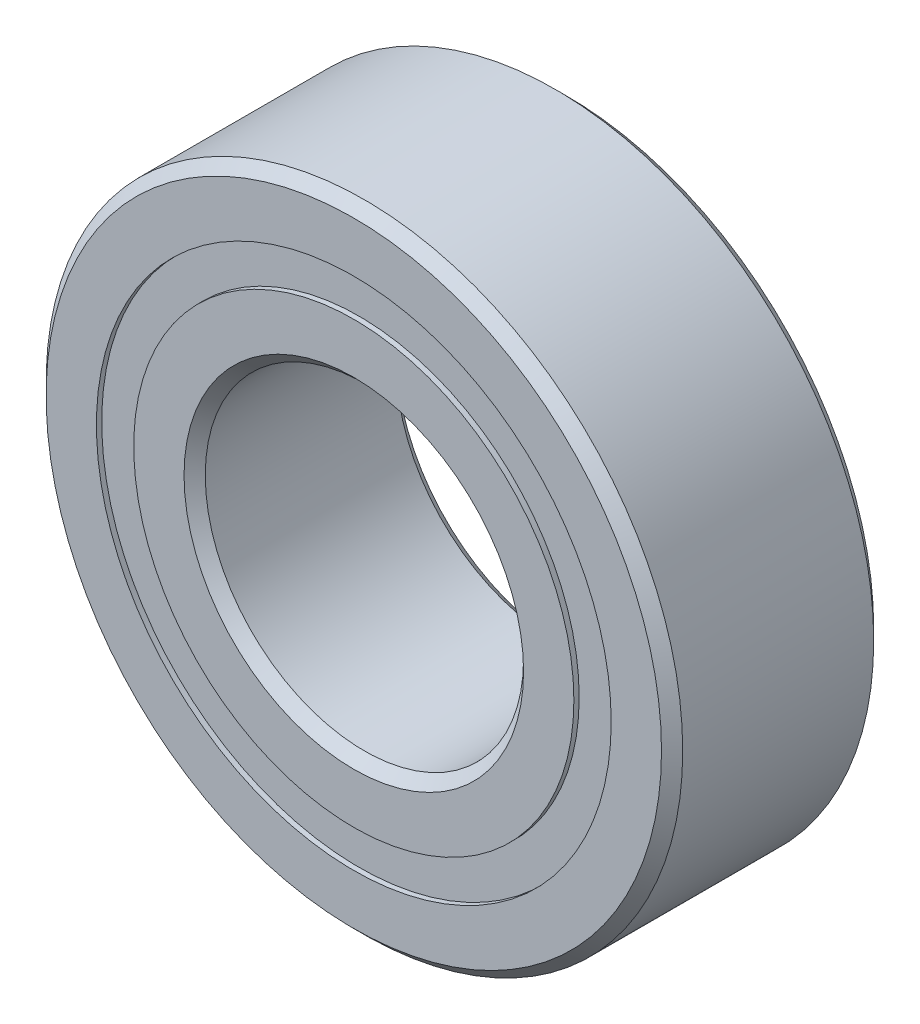
SolidWorks part; units mm, degrees
ref_plane "Front Plane" through (0, 0, 0) normal (0, 0, 1) x (1, 0, 0)
ref_plane "Top Plane" through (0, 0, 0) normal (0, 1, 0) x (1, 0, 0)
ref_plane "Right Plane" through (0, 0, 0) normal (1, 0, 0) x (0, 0, -1)
sketch "Sketch1" plane through (0, 0, 0) normal (1, 0, 0) x (0, 0, -1)
  line L0 (-2, 0) -> (2, 0) construction
  line L1 (0, 6) -> (0, -6) construction
  line L2 (1.8, 6) -> (-1.8, 6)
  line L3 (-1.8, 6) -> (-2, 5.8)
  line L4 (-2, 5.8) -> (-2, 4.8516)
  line L5 (-2, 4.8516) -> (-0.8889, 4.8516)
  line L6 (2, 4.8516) -> (0.8889, 4.8516)
  line L7 (2, 5.8) -> (2, 4.8516)
  line L8 (1.8, 6) -> (2, 5.8)
  line L9 (0, 6) -> (0, 4.5) construction
  line L10 (0, 4.5) -> (0, 3) construction
  arc A0 (-0.8889, 4.8516) -> (0.8889, 4.8516) centre (0, 4.5) cw
  point P14 (0, 3)
  dimension "D3" = 1.7778
  dimension "D1" = 45
  dimension "Width" = 4
  dimension "OD" = 12
  dimension "D2" = 0.2
  dimension "Shaft Dia" = 6
  dimension "D4" = 0.3516
revolve "Revolve1" add sketch "Sketch1" angle 360 about L0
sketch "Sketch3" plane through (0, 0, 0) normal (1, 0, 0) x (0, 0, -1)
  line L0 (-2, 4.1484) -> (-0.8889, 4.1484)
  line L1 (0, 6) -> (0, -6) construction
  line L2 (-2, 5.8) -> (-2, 4.8516) construction
  line L3 (-2, 4.1484) -> (-2, 3.2)
  line L4 (-1.8, 6) -> (-2, 5.8) construction
  line L5 (-2, 3.2) -> (-1.8, 3)
  line L6 (-1.8, 3) -> (1.8, 3)
  line L7 (1.8, 6) -> (1.8, -6) construction
  line L8 (1.8, 3) -> (2, 3.2)
  line L9 (2, -5.8) -> (2, 5.8) construction
  line L10 (2, 3.2) -> (2, 4.1484)
  line L11 (2, 4.1484) -> (0.8889, 4.1484)
  line L13 (1.8, 6) -> (2, 5.8) construction
  arc A0 (0.8889, 4.8516) -> (-0.8889, 4.8516) centre (0, 4.5) ccw construction
  arc A1 (0.8889, 4.1484) -> (-0.8889, 4.1484) centre (0, 4.5) cw
revolve "Revolve3" add sketch "Sketch3" angle 360 about L0
sketch "Sketch4" plane through (0, 0, 0) normal (1, 0, 0) x (0, 0, -1)
  line L0 (-0.9559, 4.5) -> (0.9559, 4.5)
  arc A2 (-0.9559, 4.5) -> (0.9559, 4.5) centre (0, 4.5) cw
  arc A3 (0.8889, 4.8516) -> (-0.8889, 4.8516) centre (0, 4.5) ccw construction
revolve "Revolve4" add sketch "Sketch4" angle 360 about L0
ref_axis "Axis1" through (0, 0, -2) along (0, 0, 1)
pattern_circular "CirPattern1" count 12 every 30 about axis through (0, 0, -2) along (0, 0, 1) of bodies 104
sketch "Sketch5" plane through (0, 0, 0) normal (1, 0, 0) x (0, 0, -1)
  line L0 (-2, 4.8516) -> (-0.8889, 4.8516) construction
  line L1 (-1.9, 4.8516) -> (-0.9559, 4.8516)
  line L2 (-1.9, 4.8516) -> (-1.9, 4.1484)
  line L3 (-1.9, 4.1484) -> (-0.9559, 4.1484)
  line L4 (-0.9559, 4.8516) -> (-0.9559, 4.1484)
  line L5 (-2, 4.1484) -> (-0.8889, 4.1484) construction
  line L6 (2, 4.8516) -> (0.8889, 4.8516) construction
  line L7 (1.9, 4.8516) -> (0.9559, 4.8516)
  line L8 (1.9, 4.8516) -> (1.9, 4.1484)
  line L9 (1.9, 4.1484) -> (0.9559, 4.1484)
  line L10 (0.9559, 4.8516) -> (0.9559, 4.1484)
  line L11 (2, 4.1484) -> (0.8889, 4.1484) construction
  line L12 (-1.8, 6) -> (-2, 5.8) construction
  point P18 (-1.9, 5.9)
revolve "Revolve5" add sketch "Sketch5" angle 360 about L0
sketch "Sketch6" plane through (0, 0, 0) normal (1, 0, 0) x (0, 0, -1)
  line L0 (2, 0) -> (-2, 0) construction
  line L1 (2, 4.8516) -> (1.2126, 4.8516)
  line L2 (2, 4.8516) -> (2, 6.9469)
  line L3 (2, 6.9469) -> (1.2126, 6.9469)
  line L4 (1.2126, 4.8516) -> (1.2126, 6.9469)
  dimension "Th" = 0.7874
  dimension "Flange OD" = 13.8938
revolve "Revolve6" [suppressed] add sketch "Sketch6" angle 360 about L0
equation "\"D2@Sketch1\" = \"Width@Sketch1\"*.05"
equation "\"D3@Sketch1\" = \"Width@Sketch1\"/2.25"
equation "\"D4@Sketch1\" = (((\"OD@Sketch1\"-\"Width@Sketch1\")/2)/3.25)/3.5"
equation "\"D2@CirPattern1\" = 360/\"Balls@CirPattern1\""
